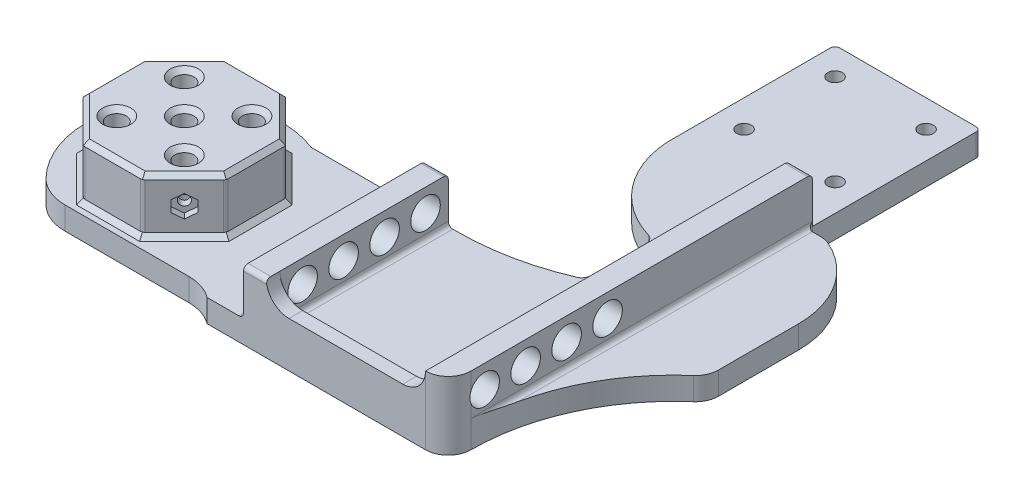
SolidWorks part; units mm, degrees
ref_plane "Спереди" through (0, 0, 0) normal (0, 0, 1) x (1, 0, 0)
ref_plane "Сверху" through (0, 0, 0) normal (0, 1, 0) x (1, 0, 0)
ref_plane "Справа" through (0, 0, 0) normal (1, 0, 0) x (0, 0, -1)
sketch "Эскиз2" plane through (0, 0, 0) normal (0, 1, 0) x (1, 0, 0)
  line L0 (0, 0) -> (32, 0)
  line L1 (0, 0) -> (0, 88)
  line L2 (32, 0) -> (32, 88)
  line L3 (0, 88) -> (32, 88)
  dimension "D1" = 88
  dimension "D2" = 32
extrude "Бобышка-Вытянуть1" add sketch "Эскиз2" along normal blind 5
sketch "Эскиз9" plane through (0, 5, 0) normal (0, 1, 0) x (1, 0, 0)
  line L0 (32, 10) -> (32, -30)
  line L1 (32, 10) -> (-68, 10)
  line L2 (32, -30) -> (-68, -30)
  line L3 (-68, 10) -> (-68, -30)
  line L4 (32, 0) -> (32, 88) construction
  line L5 (-68, -10) -> (32, -10) construction
  line L6 (32, 88) -> (0, 88) construction
  dimension "D1" = 98
  dimension "D2" = 40
  dimension "D3" = 100
extrude "Бобышка-Вытянуть6" add sketch "Эскиз9" against normal blind 5
sketch "Эскиз11" plane through (0, 5, 0) normal (0, 1, 0) x (1, 0, 0)
  line L0 (-46, -10) -> (-46, -20.5) construction
  line L1 (-46, -10) -> (-46, 0.5) construction
  line L2 (-46, -10) -> (-53.4246, -2.5754) construction
  line L3 (-46, -10) -> (-53.4246, -17.4246) construction
  line L6 (-68, -10) -> (32, -10) construction
  line L7 (-68, 10) -> (-68, -30) construction
  line L8 (32, -30) -> (32, 88) construction
  circle A0 centre (-46, -10) radius 10.5 construction
  circle A1 centre (-53.4246, -2.5754) radius 2.1
  circle A2 centre (-38.5754, -2.5754) radius 2.1
  circle A3 centre (-38.5754, -17.4246) radius 2.1
  circle A4 centre (-53.4246, -17.4246) radius 2.1
  circle A5 centre (-46, -10) radius 2.1
  point P22 (-46, -10)
  dimension "D1" = 22
  dimension "D3" = 21
  dimension "D4" = 4.2
  dimension "D5" = 4
  dimension "D2" = 45
  dimension "D7" = 4.2
extrude "Вырез-Вытянуть3" cut sketch "Эскиз11" against normal up to surface (5 mm away) up to face at (-12, 0, -22.6667)
sketch "Эскиз12" plane through (0, 0, 0) normal (0, -1, 0) x (1, 0, 0)
  circle A0 centre (-53.4246, 2.5754) radius 2.1 construction
  circle A1 centre (-53.4246, 2.5754) radius 2.1 construction
  circle A2 centre (-38.5754, 2.5754) radius 2.1 construction
  circle A3 centre (-38.5754, 2.5754) radius 2.1 construction
  circle A8 centre (-46, 10) radius 19.5
  circle A9 centre (-46, 10) radius 21.5
  circle A10 centre (-38.5754, 17.4246) radius 2.1 construction
  circle A11 centre (-38.5754, 17.4246) radius 2.1 construction
  circle A12 centre (-53.4246, 17.4246) radius 2.1 construction
  circle A13 centre (-53.4246, 17.4246) radius 2.1 construction
  circle A14 centre (-46, 10) radius 10.5 construction
  dimension "D1" = 39
  dimension "D2" = 43
extrude "Бобышка-Вытянуть7" add sketch "Эскиз12" along normal blind 8
sketch "Эскиз13" plane through (0, 5, 0) normal (0, 1, 0) x (1, 0, 0)
  line L0 (6, 81) -> (26, 81) construction
  line L1 (6, 81) -> (6, 61) construction
  line L2 (26, 81) -> (26, 61) construction
  line L3 (6, 61) -> (26, 61) construction
  line L4 (16, 81) -> (16, 61) construction
  line L5 (16, 88) -> (16, -30) construction
  line L6 (32, 88) -> (0, 88) construction
  line L7 (-68, -30) -> (32, -30) construction
  circle A0 centre (6, 81) radius 1.6
  circle A1 centre (6, 61) radius 1.6
  circle A2 centre (26, 61) radius 1.6
  circle A3 centre (26, 81) radius 1.6
  dimension "D4" = 3.2
  dimension "D5" = 3.2
  dimension "D6" = 3.2
  dimension "D7" = 3.2
  dimension "D1" = 20
  dimension "D2" = 20
  dimension "D3" = 7
extrude "Вырез-Вытянуть4" cut sketch "Эскиз13" against normal through all
sketch "Sketch1" plane through (0, 0, -88) normal (0, 0, -1) x (-1, 0, 0)
  line L4 (-32, 0) -> (0, 0)
  line L5 (0, 0) -> (0, 5)
  line L6 (0, 5) -> (-32, 5)
  line L7 (-32, 5) -> (-32, 0)
  line L8 (-32, 0) -> (0, 0)
  line L9 (0, 0) -> (0, 5)
  line L10 (0, 5) -> (-32, 5)
  line L11 (-32, 5) -> (-32, 0)
  dimension "D1" = 0
extrude "Cut-Extrude1" cut sketch "Sketch1" against normal blind 1
sketch "Эскиз14" plane through (0, 0, 0) normal (0, -1, 0) x (1, 0, 0)
  line L3 (-53.8899, 30) -> (-68, 30)
  line L4 (-68, 30) -> (-68, -10)
  line L5 (-68, -10) -> (-53.8899, -10)
  line L6 (-53.8899, 30) -> (-68, 30)
  line L7 (-68, 30) -> (-68, -10)
  line L8 (-68, -10) -> (-53.8899, -10)
  arc A1 (-53.8899, 30) -> (-53.8899, -10) centre (-46, 10) ccw
  arc A2 (-53.8899, 30) -> (-53.8899, -10) centre (-46, 10) ccw
  dimension "D1" = 0
extrude "Вырез-Вытянуть5" cut sketch "Эскиз14" against normal through all
sketch "Эскиз15" plane through (0, 0, 0) normal (0, 1, 0) x (1, 0, 0)
  line L1 (-38.1101, -30) -> (-53.8899, -30)
  line L2 (-38.1101, -30) -> (-53.8899, -30)
  line L3 (-53.8899, 10) -> (-38.1101, 10)
  line L4 (-53.8899, 10) -> (-38.1101, 10)
  arc A1 (-53.8899, -30) -> (-38.1101, -30) centre (-46, -10) ccw
  arc A2 (-53.8899, -30) -> (-38.1101, -30) centre (-46, -10) ccw
  arc A3 (-38.1101, 10) -> (-53.8899, 10) centre (-46, -10) ccw
  arc A4 (-38.1101, 10) -> (-53.8899, 10) centre (-46, -10) ccw
  dimension "D1" = 0
  dimension "D2" = 0
extrude "Бобышка-Вытянуть8" add sketch "Эскиз15" along normal up to surface (5 mm away) up to face at (-53.4246, 5, 4.6754)
sketch "Эскиз16" plane through (0, 5, 0) normal (0, 1, 0) x (1, 0, 0)
  line L0 (-13, 10) -> (-8, 10)
  line L1 (-13, 10) -> (-13, -30)
  line L2 (-8, 10) -> (-8, -30)
  line L3 (-13, -30) -> (-8, -30)
  line L4 (0, 10) -> (-38.1101, 10) construction
  line L5 (-38.1101, -30) -> (32, -30) construction
  line L6 (32, -30) -> (32, 87) construction
  line L7 (27, -30) -> (32, -30)
  line L8 (27, -30) -> (27, 50)
  line L9 (32, -30) -> (32, 50)
  line L10 (27, 50) -> (32, 50)
  dimension "D1" = 5
  dimension "D2" = 45
  dimension "D3" = 5
  dimension "D4" = 80
extrude "Бобышка-Вытянуть9" add sketch "Эскиз16" along normal blind 10
sketch "Эскиз17" plane through (0, 5, 0) normal (0, 1, 0) x (1, 0, 0)
  line L0 (-8, -30) -> (-8, -27)
  line L1 (-8, -30) -> (27, -30)
  line L2 (-8, -27) -> (27, -27)
  line L3 (27, -30) -> (27, -27)
  line L4 (-8, -30) -> (-8, 10) construction
  line L5 (27, 50) -> (27, -30) construction
  dimension "D1" = 3
extrude "Бобышка-Вытянуть10" add sketch "Эскиз17" along normal blind 5
sketch "Эскиз18" plane through (-8, 0, 0) normal (1, 0, 0) x (0, 0, -1)
  line L0 (10, 10) -> (-41.8716, 10) construction
  line L1 (10, 15) -> (10, 5) construction
  circle A0 centre (5, 10) radius 3.25
  circle A1 centre (-4, 10) radius 3.25
  circle A2 centre (-13, 10) radius 3.25
  circle A3 centre (-22, 10) radius 3.25
  dimension "D1" = 6.5
  dimension "D2" = 6.5
  dimension "D3" = 6.5
  dimension "D4" = 6.5
  dimension "D5" = 5
  dimension "D6" = 9
  dimension "D7" = 9
  dimension "D8" = 9
extrude "Вырез-Вытянуть6" cut sketch "Эскиз18" against normal through all
sketch "Эскиз19" plane through (32, 0, 0) normal (1, 0, 0) x (0, 0, -1)
  line L0 (50, 10) -> (-21.4049, 10) construction
  line L1 (50, 15) -> (50, 5) construction
  circle A0 centre (41, 10) radius 3.25
  circle A1 centre (32, 10) radius 3.25
  circle A2 centre (23, 10) radius 3.25
  circle A3 centre (14, 10) radius 3.25
  dimension "D1" = 6.5
  dimension "D2" = 6.5
  dimension "D3" = 6.5
  dimension "D4" = 6.5
  dimension "D5" = 9
  dimension "D6" = 9
  dimension "D7" = 9
  dimension "D8" = 9
fillet "Скругление5" radius 1 4 edges at (27, 5, -11.5) (9.5, 5, 27)
fillet "Скругление6" radius 5 2 edges at (27, 10, 28.5) (-8, 10, 28.5)
fillet "Скругление7" radius 1 2 edges at (32, 2.5, -87) (0, 2.5, -87)
fillet "Скругление8" radius 1 3 edges at (-10.5, 15, 30) (-10.5, 15, -10) (29.5, 15, -50)
sketch "Эскиз20" plane through (0, -8, 0) normal (0, -1, 0) x (1, 0, 0)
  circle A1 centre (-46, 10) radius 21.5
  circle A2 centre (-46, 10) radius 21.5
  dimension "D1" = 0
extrude "Вырез-Вытянуть8" cut sketch "Эскиз20" against normal up to surface (8 mm away) up to face at (26, 0, -82.6)
sketch "Эскиз21" plane through (0, 5, 0) normal (0, 1, 0) x (1, 0, 0)
  line L0 (-57.758, -28) -> (-27, -28)
  line L1 (-38.1101, -30) -> (-14, -30) construction
  line L2 (-13, 10) -> (-13, -30) construction
  line L3 (-38.1101, -30) -> (-21, -30)
  arc A0 (-38.1101, 10) -> (-38.1101, -30) centre (-46, -10) ccw construction
  arc A1 (-27, -28) -> (-21, -30) centre (-27, -38) cw
  arc A2 (-57.758, -28) -> (-38.1101, -30) centre (-46, -10) ccw
  dimension "D1" = 2
  dimension "D2" = 10
  dimension "D3" = 8
extrude "Вырез-Вытянуть9" cut sketch "Эскиз21" against normal through all
fillet "Скругление9" radius 10 1 edges at (-57.758, 2.5, 28)
sketch "Эскиз22" plane through (0, 0, 0) normal (-1, 0, 0) x (0, 0, 1)
  line L0 (-50, 14) -> (-50, 6) construction
  line L1 (-50, 5) -> (-50, 0) construction
  line L2 (-86, 5) -> (-10, 5) construction
  line L3 (-86, 0) -> (-10, 0) construction
  line L4 (-50, 5) -> (-10, 5)
  line L5 (-50, 0) -> (-10, 0)
  line L6 (-10, 0) -> (-10, 5) construction
  line L7 (-10, 0) -> (-10, 5)
  line L8 (-50, 5) -> (-50, 0)
extrude "Вырез-Вытянуть10" cut sketch "Эскиз22" against normal blind 17
sketch "Эскиз23" plane through (32, 0, 0) normal (1, 0, 0) x (0, 0, -1)
  line L4 (10, 5) -> (10, 0)
  line L5 (50, 5) -> (10, 5)
  line L6 (50, 0) -> (50, 5)
  line L7 (10, 0) -> (50, 0)
  line L8 (10, 5) -> (10, 0)
  line L9 (50, 5) -> (10, 5)
  line L10 (50, 0) -> (50, 5)
  line L11 (10, 0) -> (50, 0)
  dimension "D1" = 0
extrude "Бобышка-Вытянуть11" add sketch "Эскиз23" along normal blind 17
sketch "Эскиз25" plane through (0, 5, 0) normal (0, 1, 0) x (1, 0, 0)
  line L0 (17, 15) -> (17, 10)
  line L1 (17, 10) -> (17, 50) construction
  line L2 (17, 10) -> (-6, 10)
  line L3 (17, 10) -> (-7, 10) construction
  line L6 (17, 30) -> (17, 50)
  line L7 (17, 50) -> (0, 50)
  arc A0 (17, 30) -> (0, 50) centre (21.9531, 51.4352) cw
  arc A1 (17, 15) -> (-6, 10) centre (-6, 65.4) cw
  dimension "D4" = 22
  dimension "D1" = 5
  dimension "D2" = 23
  dimension "D3" = 15
  dimension "D5" = 20
extrude "Бобышка-Вытянуть12" add sketch "Эскиз25" against normal up to surface (5 mm away) up to face at (4.4666, 0, -26.743)
fillet "Скругление10" radius 2 2 edges at (17, 2.5, -15) (17, 2.5, -30)
sketch "Эскиз26" plane through (0, 5, 0) normal (0, 1, 0) x (1, 0, 0)
  line L0 (32, 30) -> (49, 30) construction
  line L1 (32, 50) -> (32, 10) construction
  line L3 (49, 50) -> (49, 10) construction
  line L4 (32, 50) -> (32, 30) construction
  line L5 (49, 50) -> (32, 50) construction
  line L6 (49, 50) -> (32, 50)
  line L7 (49, 50) -> (49, 30)
  arc A0 (49, 30) -> (32, 50) centre (28.7353, 30) ccw
  dimension "D1" = 20
extrude "Вырез-Вытянуть11" cut sketch "Эскиз26" against normal through all
sketch "Эскиз27" plane through (0, 5, 0) normal (0, 1, 0) x (1, 0, 0)
  line L0 (49, 10) -> (32, 10) construction
  line L1 (49, 10) -> (32, 10)
  line L2 (32, 10) -> (32, -25)
  arc A0 (49, 10) -> (32, -25) centre (76.5294, -25) ccw
  dimension "D1" = 35
extrude "Бобышка-Вытянуть13" add sketch "Эскиз27" against normal up to surface (5 mm away) up to face at (5.1363, 0, -23.6939)
fillet "Скругление12" radius 5 1 edges at (32, 7.5, 30)
fillet "Скругление13" radius 1 1 edges at (32, 5, -12.5)
sketch "Эскиз28" plane through (32, 0, 0) normal (1, 0, 0) x (0, 0, -1)
  circle A0 centre (5, 10) radius 3.25 construction
  circle A1 centre (-4, 10) radius 3.25 construction
  circle A2 centre (-13, 10) radius 3.25 construction
  circle A3 centre (-22, 10) radius 3.25 construction
  circle A4 centre (5, 10) radius 3.25
  circle A5 centre (-4, 10) radius 3.25
  circle A6 centre (-13, 10) radius 3.25
  circle A7 centre (-22, 10) radius 3.25
extrude "Вырез-Вытянуть12" cut sketch "Эскиз28" against normal up to surface (5 mm away) up to face at (27, 11.2414, -19.0414)
fillet "Скругление14" radius 5 1 edges at (49, 2.5, -10)
sketch "Эскиз29" plane through (0, 0, -50) normal (0, 0, -1) x (-1, 0, 0)
  line L0 (-32, 0) -> (-32, 5) construction
  line L1 (-32, 0) -> (-32, 8)
  line L2 (-32, 14) -> (-32, 6) construction
  line L3 (-32, 8) -> (-37, 8)
  line L4 (-37, 8) -> (-37, 0)
  line L5 (-37, 0) -> (-32, 0)
  dimension "D1" = 5
  dimension "D2" = 8
extrude "Вырез-Вытянуть13" cut sketch "Эскиз29" against normal blind 1
fillet "Скругление15" radius 1 1 edges at (32, 3, -49)
fillet "Скругление16" radius 5 1 edges at (35.7822, 2.5, -49)
sketch "Эскиз33" plane through (0, 5, 0) normal (0, 1, 0) x (1, 0, 0)
  line L0 (-46, -10) -> (-46, 5.75) construction
  line L1 (-52.5239, -25.75) -> (-39.4761, -25.75)
  line L2 (-39.4761, -25.75) -> (-30.25, -16.5239)
  line L3 (-30.25, -16.5239) -> (-30.25, -3.4761)
  line L4 (-30.25, -3.4761) -> (-39.4761, 5.75)
  line L5 (-39.4761, 5.75) -> (-52.5239, 5.75)
  line L6 (-52.5239, 5.75) -> (-61.75, -3.4761)
  line L7 (-61.75, -3.4761) -> (-61.75, -16.5239)
  line L8 (-61.75, -16.5239) -> (-52.5239, -25.75)
  line L9 (-27, -28) -> (-54.2614, -28) construction
  circle A0 centre (-46, -10) radius 15.75 construction
  circle A2 centre (-53.4246, -2.5754) radius 2.1 construction
  circle A3 centre (-46, -10) radius 2.1 construction
  circle A4 centre (-53.4246, -17.4246) radius 2.1 construction
  circle A5 centre (-38.5754, -2.5754) radius 2.1 construction
  circle A6 centre (-38.5754, -17.4246) radius 2.1 construction
  circle A7 centre (-53.4246, -2.5754) radius 2.1
  circle A8 centre (-46, -10) radius 2.1
  circle A9 centre (-53.4246, -17.4246) radius 2.1
  circle A10 centre (-38.5754, -2.5754) radius 2.1
  circle A11 centre (-38.5754, -17.4246) radius 2.1
  dimension "D1" = 2.25
extrude "Бобышка-Вытянуть15" add sketch "Эскиз33" along normal blind 12
sketch "Эскиз37" plane through (-6.8631, 0, -6.8631) normal (0.7071, 0, 0.7071) x (0.7071, 0, -0.7071)
  line L0 (-39.598, 17) -> (-39.598, 5) construction
  line L1 (-46.1218, 17) -> (-33.0741, 17) construction
  line L2 (-46.1218, 5) -> (-33.0741, 5) construction
  circle A0 centre (-39.598, 11) radius 1.1
  dimension "D1" = 2.2
extrude "Вырез-Вытянуть15" cut sketch "Эскиз37" against normal up to surface (3.4611 mm away) up to face at (-38.5754, 0, 15.3246)
sketch "Эскиз38" plane through (-6.8631, 0, -6.8631) normal (0.7071, 0, 0.7071) x (0.7071, 0, -0.7071)
  line L0 (-39.598, 11) -> (-39.598, 13.4249) construction
  line L1 (-39.598, 8.5751) -> (-37.498, 9.7876)
  line L2 (-37.498, 9.7876) -> (-37.498, 12.2124)
  line L3 (-37.498, 12.2124) -> (-39.598, 13.4249)
  line L4 (-39.598, 13.4249) -> (-41.698, 12.2124)
  line L5 (-41.698, 12.2124) -> (-41.698, 9.7876)
  line L6 (-41.698, 9.7876) -> (-39.598, 8.5751)
  circle A0 centre (-39.598, 11) radius 2.1 construction
  dimension "D1" = 4.2
extrude "Вырез-Вытянуть16" cut sketch "Эскиз38" against normal blind 1.6
sketch "Эскиз39" plane through (-39.1369, 0, 39.1369) normal (-0.7071, 0, 0.7071) x (0.7071, 0, 0.7071)
  line L0 (-25.4558, 17) -> (-25.4558, 5) construction
  line L1 (-31.9797, 17) -> (-18.932, 17) construction
  line L2 (-31.9797, 5) -> (-18.932, 5) construction
  circle A0 centre (-25.4558, 11) radius 1.1
  dimension "D1" = 2.2
extrude "Вырез-Вытянуть17" cut sketch "Эскиз39" against normal up to surface (3.4611 mm away) up to face at (-53.4246, 0, 15.3246)
sketch "Эскиз41" plane through (-39.1369, 0, 39.1369) normal (-0.7071, 0, 0.7071) x (0.7071, 0, 0.7071)
  line L0 (-25.4558, 11) -> (-25.4558, 13.4249) construction
  line L1 (-25.4558, 8.5751) -> (-23.3558, 9.7876)
  line L2 (-23.3558, 9.7876) -> (-23.3558, 12.2124)
  line L3 (-23.3558, 12.2124) -> (-25.4558, 13.4249)
  line L4 (-25.4558, 13.4249) -> (-27.5558, 12.2124)
  line L5 (-27.5558, 12.2124) -> (-27.5558, 9.7876)
  line L6 (-27.5558, 9.7876) -> (-25.4558, 8.5751)
  circle A0 centre (-25.4558, 11) radius 2.1 construction
  dimension "D1" = 4.2
extrude "Вырез-Вытянуть18" cut sketch "Эскиз41" against normal blind 1.6
sketch "Эскиз42" plane through (-61.75, 0, 0) normal (-1, 0, 0) x (0, 0, 1)
  line L0 (10, 17) -> (10, 5) construction
  line L1 (3.4761, 17) -> (16.5239, 17) construction
  line L2 (3.4761, 5) -> (16.5239, 5) construction
  circle A0 centre (10, 11) radius 1.1
  dimension "D1" = 2.2
extrude "Вырез-Вытянуть19" cut sketch "Эскиз42" against normal up to surface (13.9611 mm away) up to face at (-46, 0, 7.9)
sketch "Эскиз43" plane through (-61.75, 0, 0) normal (-1, 0, 0) x (0, 0, 1)
  line L0 (10, 11) -> (10, 13.4249) construction
  line L1 (10, 13.4249) -> (7.9, 12.2124)
  line L2 (7.9, 12.2124) -> (7.9, 9.7876)
  line L3 (7.9, 9.7876) -> (10, 8.5751)
  line L4 (10, 8.5751) -> (12.1, 9.7876)
  line L5 (12.1, 9.7876) -> (12.1, 12.2124)
  line L6 (12.1, 12.2124) -> (10, 13.4249)
  circle A0 centre (10, 11) radius 2.1 construction
  dimension "D1" = 4.2
extrude "Вырез-Вытянуть20" cut sketch "Эскиз43" against normal blind 1.6
sketch "Эскиз44" plane through (-29.1369, 0, -29.1369) normal (-0.7071, 0, -0.7071) x (-0.7071, 0, 0.7071)
  line L0 (39.598, 17) -> (39.598, 5) construction
  line L1 (33.0741, 17) -> (46.1218, 17) construction
  line L2 (33.0741, 5) -> (46.1218, 5) construction
  circle A0 centre (39.598, 11) radius 1.1
  dimension "D1" = 2.2
extrude "Вырез-Вытянуть21" cut sketch "Эскиз44" against normal up to surface (3.4611 mm away) up to face at (-53.4246, 0, 0.4754)
sketch "Эскиз45" plane through (-29.1369, 0, -29.1369) normal (-0.7071, 0, -0.7071) x (-0.7071, 0, 0.7071)
  line L0 (39.598, 11) -> (39.598, 13.4249) construction
  line L1 (39.598, 13.4249) -> (37.498, 12.2124)
  line L2 (37.498, 12.2124) -> (37.498, 9.7876)
  line L3 (37.498, 9.7876) -> (39.598, 8.5751)
  line L4 (39.598, 8.5751) -> (41.698, 9.7876)
  line L5 (41.698, 9.7876) -> (41.698, 12.2124)
  line L6 (41.698, 12.2124) -> (39.598, 13.4249)
  circle A0 centre (39.598, 11) radius 2.1 construction
  dimension "D1" = 4.2
extrude "Вырез-Вытянуть22" cut sketch "Эскиз45" against normal blind 1.6
sketch "Эскиз46" plane through (-16.8631, 0, 16.8631) normal (0.7071, 0, -0.7071) x (-0.7071, 0, -0.7071)
  line L0 (25.4558, 17) -> (25.4558, 5) construction
  line L1 (18.932, 17) -> (31.9797, 17) construction
  line L2 (18.932, 5) -> (31.9797, 5) construction
  circle A0 centre (25.4558, 11) radius 1.1
  dimension "D1" = 2.2
extrude "Вырез-Вытянуть23" cut sketch "Эскиз46" against normal up to surface (3.4611 mm away) up to face at (-38.5754, 0, 0.4754)
sketch "Эскиз47" plane through (-16.8631, 0, 16.8631) normal (0.7071, 0, -0.7071) x (-0.7071, 0, -0.7071)
  line L0 (25.4558, 11) -> (25.4558, 13.4249) construction
  line L1 (25.4558, 13.4249) -> (23.3558, 12.2124)
  line L2 (23.3558, 12.2124) -> (23.3558, 9.7876)
  line L3 (23.3558, 9.7876) -> (25.4558, 8.5751)
  line L4 (25.4558, 8.5751) -> (27.5558, 9.7876)
  line L5 (27.5558, 9.7876) -> (27.5558, 12.2124)
  line L6 (27.5558, 12.2124) -> (25.4558, 13.4249)
  circle A0 centre (25.4558, 11) radius 2.1 construction
  dimension "D1" = 4.2
extrude "Вырез-Вытянуть24" cut sketch "Эскиз47" against normal blind 1.6
chamfer "Фаска1" distance 1 angle 45 8 edges at (-34.8631, 5, 21.1369) (-30.25, 5, 10) (-34.8631, 5, -1.1369) (-46, 5, -5.75) (-57.1369, 5, -1.1369) (-61.75, 5, 10) (-57.1369, 5, 21.1369) (-46, 5, 25.75)
chamfer "Фаска2" distance 1 angle 45 13 edges at (-38.5754, 17, 19.5246) (-53.4246, 17, 19.5246) (-53.4246, 17, 4.6754) (-61.75, 17, 10) (-57.1369, 17, -1.1369) (-46, 17, -5.75) (-34.8631, 17, -1.1369) (-30.25, 17, 10) (-34.8631, 17, 21.1369) (-46, 17, 25.75) (-57.1369, 17, 21.1369) (-46, 17, 12.1) (-38.5754, 17, 4.6754)
fillet "Скругление17" radius 1 8 edges at (-39.4761, 11, -5.75) (-30.25, 11, 3.4761) (-30.25, 11, 16.5239) (-39.4761, 11, 25.75) (-52.5239, 11, 25.75) (-61.75, 11, 16.5239) (-52.5239, 11, -5.75) (-61.75, 11, 3.4761)
